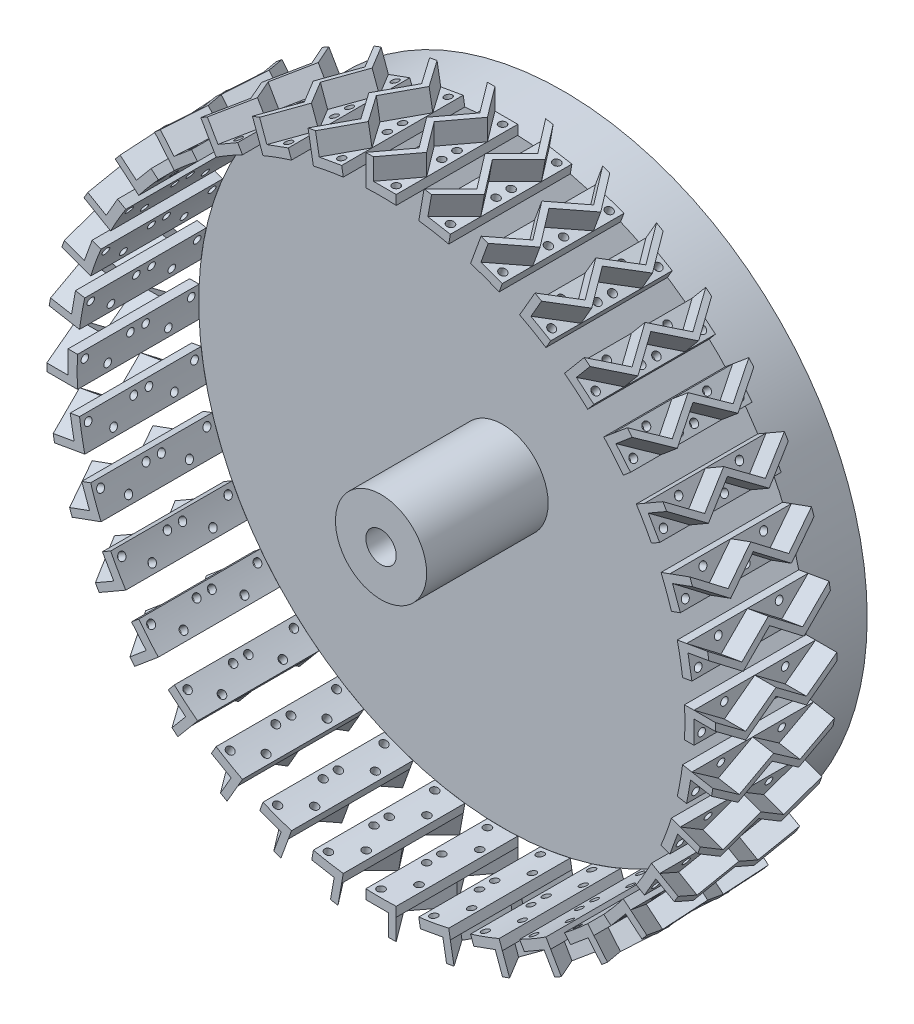
SolidWorks part; units mm, degrees
material "Polyetheretherketone (PEEK)"
ref_plane "Front Plane" through (0, 0, 0) normal (0, 0, 1) x (1, 0, 0)
ref_plane "Top Plane" through (0, 0, 0) normal (0, 1, 0) x (1, 0, 0)
ref_plane "Right Plane" through (0, 0, 0) normal (1, 0, 0) x (0, 0, -1)
sketch "Sketch1" plane through (0, 0, 0) normal (0, 0, 1) x (1, 0, 0)
  circle A0 centre (0, 0) radius 127
  dimension "D1" = 254
extrude "Boss-Extrude1" add sketch "Sketch1" along normal blind 50.8
ref_plane "Plane1" through (139.7, 0, 0) normal (1, 0, 0) x (0, 0, -1)
sketch "Sketch2" plane through (139.7, 0, 0) normal (1, 0, 0) x (0, 0, -1)
  line L0 (0, 0) -> (-25.4, 0)
  line L1 (0, 6.35) -> (-25.4, 6.35)
  line L2 (0, -6.35) -> (-25.4, -6.35)
  line L3 (-25.4, 0) -> (-25.4, -6.35)
  line L4 (0, 6.35) -> (0, -6.35)
  line L5 (-25.4, 6.35) -> (-12.7, -3.175)
  line L6 (-12.7, -3.175) -> (0, 6.35)
  line L7 (-25.4, 3.175) -> (-12.7, -6.35)
  line L8 (-12.7, -6.35) -> (0, 3.175)
  line L9 (-25.4, 6.35) -> (-25.4, 0)
  circle A0 centre (-22.225, -3.175) radius 1.5875
  circle A1 centre (-12.7, 3.175) radius 1.5875
  circle A2 centre (-3.175, -3.175) radius 1.5875
  dimension "D6" = 3.175
  dimension "D1" = 25.4
  dimension "D4" = 3.175
  dimension "D5" = 3.175
  dimension "D7" = 3.175
  dimension "D8" = 3.175
  dimension "D9" = 3.175
  dimension "D2" = 6.35
  dimension "D3" = 6.35
extrude "Boss-Extrude2" add sketch "Sketch2" against normal blind 15.24 separate body contours L8 L2 L4 L0 A2 | L8 L0 L4 | L0 L6 L1 L5 A1 | L5 L6 L0 | L7 L0 L3 L2 A0 | L7 L9 L0 | L7 L8 L0 L6 L5 | L5 L9 L7 L0 | L0 L8 L4 L6 region at (139.7, -3.7956, 4.8298) region at (139.7, 1.0583, 1.4111) region at (139.7, -3.0303, 8.5752) region at (139.7, 2.4694, 3.2926) region at (139.7, -1.0583, 12.7) region at (139.7, 0.2618, 12.7) region at (139.7, -3.7956, 20.5702) region at (139.7, 2.4694, 22.1074) region at (139.7, 1.0583, 23.9889)
extrude "Cut-Extrude1" cut sketch "Sketch2<4>" against normal blind 8.89 contours L8 L2 L4 L0 A2 | L8 L0 L4 | L0 L6 L1 L5 A1 | L7 L9 L0 | L5 L6 L0 | L7 L0 L3 L2 A0 region at (139.7, -3.7956, 4.8298) region at (139.7, 1.0583, 1.4111) region at (139.7, -1.0583, 12.7) region at (139.7, 0.2618, 12.7) region at (139.7, -3.7956, 20.5702) region at (139.7, 1.0583, 23.9889)
sketch "Sketch2<4>" plane through (139.7, 0, 0) normal (1, 0, 0) x (0, 0, -1) same geometry as "Sketch2"
pattern_linear "LPattern1" count 2 spacing 25.4 along (0, 0, 1) of bodies 105
combine bodies "Combine1" operation type add bodies to combine 106 105
extrude "Cut-Extrude2" cut sketch "Sketch1<2>" along normal blind 101.6
sketch "Sketch1<2>" plane through (0, 0, 0) normal (0, 0, 1) x (1, 0, 0) same geometry as "Sketch1"
extrude "Boss-Extrude3" add sketch "Sketch1<3>" against normal blind 25.4 separate body
sketch "Sketch1<3>" plane through (0, 0, 0) normal (0, 0, 1) x (1, 0, 0) same geometry as "Sketch1"
pattern_circular "CirPattern1" count 36 over 360 about axis through (0, 0, 0) along (0, 0, 1) of bodies 108
sketch "Sketch4" plane through (0, 0, 50.8) normal (0, 0, 1) x (1, 0, 0)
  circle A0 centre (0, 0) radius 6.35
  circle A1 centre (0, 0) radius 19.05
  dimension "D1" = 12.7
  dimension "D2" = 38.1
extrude "Boss-Extrude4" add sketch "Sketch4" against normal blind 50.8 separate body
